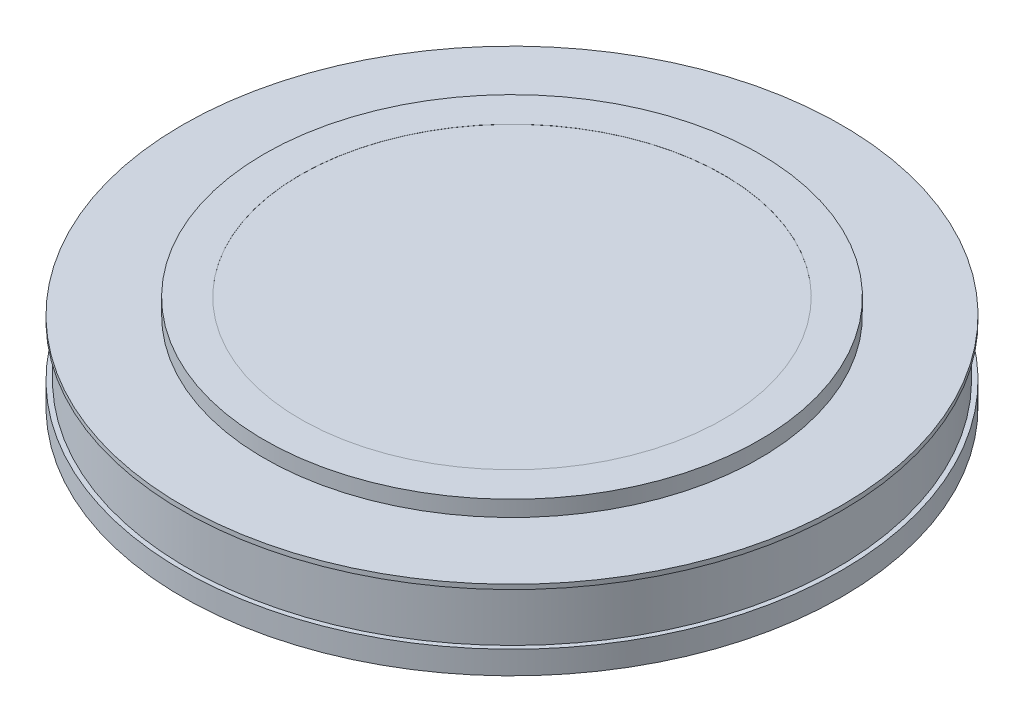
SolidWorks part; units mm, degrees
ref_plane "Alzado" through (0, 0, 0) normal (0, 0, 1) x (1, 0, 0)
ref_plane "Planta" through (0, 0, 0) normal (0, 1, 0) x (1, 0, 0)
ref_plane "Vista lateral" through (0, 0, 0) normal (1, 0, 0) x (0, 0, -1)
sketch "Croquis2" plane through (0, 0, 0) normal (0, 0, 1) x (1, 0, 0)
  line L0 (125.9, 0) -> (142.9, 0)
  line L1 (142.9, 0) -> (142.9, 10)
  line L2 (142.9, 10) -> (140.9, 10)
  line L15 (140.9, 32.4) -> (142.9, 32.4)
  line L16 (142.9, 32.4) -> (142.9, 34.4)
  line L19 (91.7615, 41.1979) -> (0, 41.1979)
  line L22 (125.9, 31.4) -> (125.9, 0)
  line L23 (142.9, 34.4) -> (107.45, 34.4)
  line L24 (107.45, 34.4) -> (107.45, 41.25)
  line L25 (107.45, 41.25) -> (91.7615, 41.25)
  line L28 (91.7615, 41.25) -> (91.7615, 41.1979)
  line L29 (140.9, 32.4) -> (140.9, 10)
  line L30 (0, 41.1979) -> (0, 38.1979)
  line L31 (0, 38.1979) -> (104.45, 38.1979)
  line L32 (104.45, 38.1979) -> (104.45, 31.4)
  line L33 (104.45, 31.4) -> (125.9, 31.4)
  dimension "D1" = 10
  dimension "D2" = 2
  dimension "D3" = 34.4
  dimension "D4" = 2
  dimension "D5" = 6.85
  dimension "D6" = 3
  dimension "D7" = 142.9
  dimension "D8" = 2
  dimension "D9" = 17
  dimension "D10" = 3
  dimension "D11" = 15.6885
  dimension "D12" = 35.45
  dimension "D13" = 3
  dimension "D14" = 3
revolve "Revolución1" add sketch "Croquis2" angle 360 about L30
